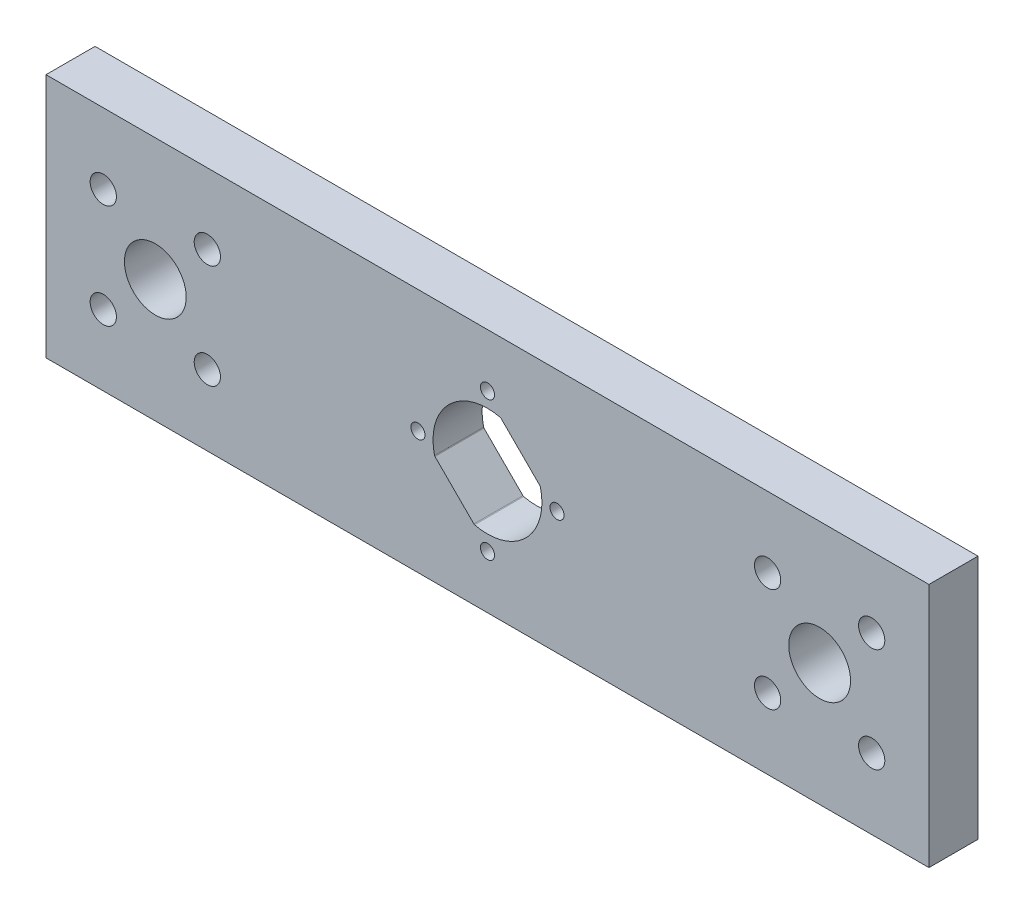
SolidWorks part; units mm, degrees
ref_plane "Front Plane" through (0, 0, 0) normal (0, 0, 1) x (1, 0, 0)
ref_plane "Top Plane" through (0, 0, 0) normal (0, 1, 0) x (1, 0, 0)
ref_plane "Right Plane" through (0, 0, 0) normal (1, 0, 0) x (0, 0, -1)
sketch "Sketch1" plane through (0, 0, 0) normal (0, 0, 1) x (1, 0, 0)
  line L0 (-6.7979, -1.7581) -> (-1.7581, -6.7979)
  line L1 (-57.15, 15.875) -> (57.15, 15.875)
  line L2 (-57.15, 15.875) -> (-57.15, -15.875)
  line L3 (-57.15, -15.875) -> (57.15, -15.875)
  line L4 (57.15, 15.875) -> (57.15, -15.875)
  line L5 (-57.15, 15.875) -> (57.15, -15.875) construction
  line L6 (-57.15, -15.875) -> (57.15, 15.875) construction
  line L7 (6.7979, 1.7581) -> (1.7581, 6.7979)
  line L16 (0, 9) -> (0, -9) construction
  line L17 (-9, 0) -> (9, 0) construction
  line L18 (-57.15, 0) -> (57.15, 0) construction
  line L19 (0, 15.875) -> (0, -15.875) construction
  line L20 (-43, 0) -> (-36.2648, 6.7352) construction
  line L21 (-43, -4) -> (-43, 4) construction
  line L22 (-43, 0) -> (-49.7352, 6.7352) construction
  line L23 (-43, 0) -> (-36.2648, -6.7352) construction
  line L24 (-43, 0) -> (-49.7352, -6.7352) construction
  line L25 (43, 0) -> (49.7352, -6.7352) construction
  line L26 (43, -4) -> (43, 4) construction
  line L27 (43, 0) -> (36.2648, -6.7352) construction
  line L28 (43, 0) -> (36.2648, 6.7352) construction
  line L29 (43, 0) -> (49.7352, 6.7352) construction
  circle A8 centre (-9, 0) radius 0.9115
  circle A9 centre (0, -9) radius 0.9115
  arc A10 (1.7581, 6.7979) -> (1.6639, 6.8508) centre (1.6167, 6.6565) ccw
  arc A11 (-6.8508, -1.6639) -> (-6.7979, -1.7581) centre (-6.6565, -1.6167) ccw
  arc A12 (1.6639, 6.8508) -> (-6.8508, -1.6639) centre (0, 0) ccw
  arc A13 (-1.7581, -6.7979) -> (-1.6639, -6.8508) centre (-1.6167, -6.6565) ccw
  arc A14 (-1.6639, -6.8508) -> (6.8508, 1.6639) centre (0, 0) ccw
  arc A15 (6.8508, 1.6639) -> (6.7979, 1.7581) centre (6.6565, 1.6167) ccw
  circle A16 centre (9, 0) radius 0.9115
  circle A17 centre (0, 9) radius 0.9115
  circle A22 centre (-43, 0) radius 4
  circle A23 centre (43, 0) radius 4
  circle A24 centre (-36.2648, 6.7352) radius 1.7
  circle A25 centre (-49.7352, 6.7352) radius 1.7
  circle A26 centre (-36.2648, -6.7352) radius 1.7
  circle A27 centre (-49.7352, -6.7352) radius 1.7
  circle A28 centre (49.7352, -6.7352) radius 1.7
  circle A29 centre (36.2648, -6.7352) radius 1.7
  circle A30 centre (36.2648, 6.7352) radius 1.7
  circle A31 centre (49.7352, 6.7352) radius 1.7
  point P0 (0, 0)
  dimension "D5" = 1.823
  dimension "D6" = 1.823
  dimension "D7" = 1.823
  dimension "D8" = 1.823
  dimension "D9" = 8
  dimension "D10" = 8
  dimension "D13" = 3.4
  dimension "D1" = 114.3
  dimension "D2" = 31.75
  dimension "D3" = 18
  dimension "D4" = 18
  dimension "D11" = 43
  dimension "D12" = 43
  dimension "D14" = 45
  dimension "D15" = 9.525
  dimension "D16" = 9.525
extrude "Boss-Extrude1" add sketch "Sketch1" along normal blind 6.35
equation "\"MOTOR_CENTER_DIST\" = 43mm"
equation "\"D11@Sketch1\"=\"MOTOR_CENTER_DIST\""
equation "\"D12@Sketch1\"=\"MOTOR_CENTER_DIST\""
